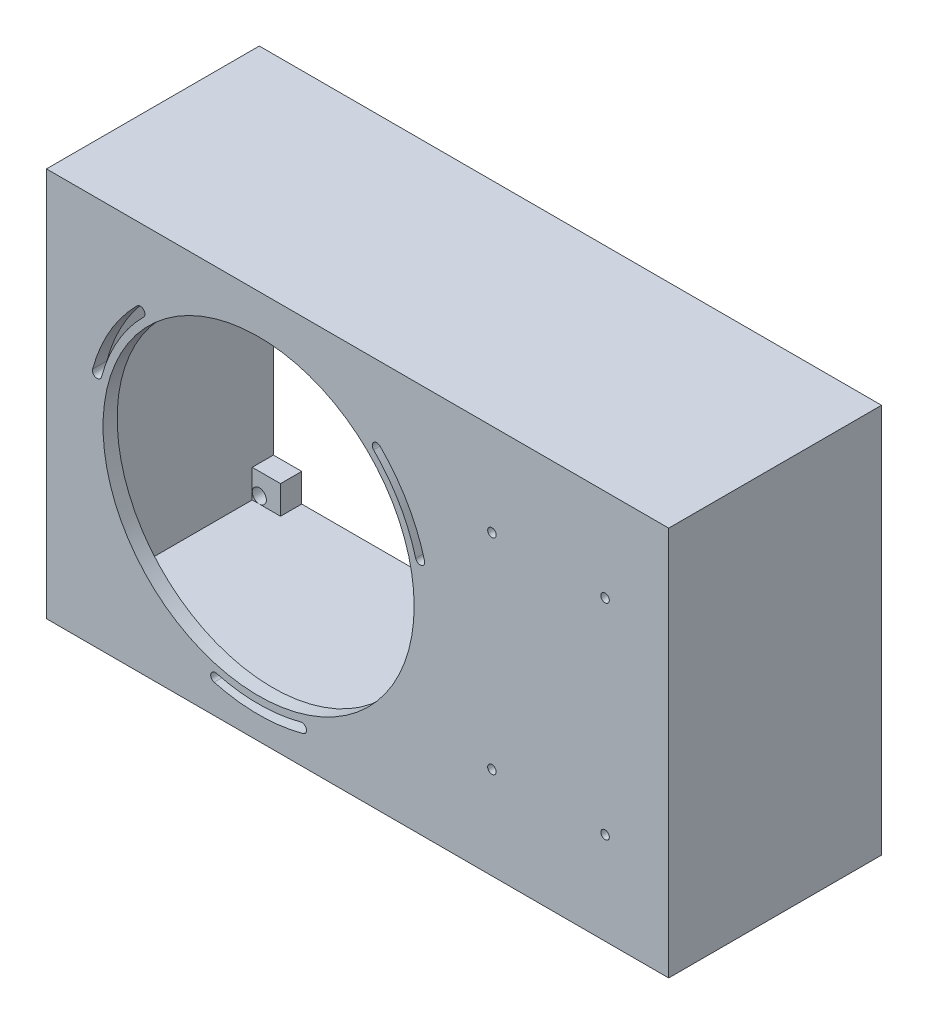
SolidWorks part; units mm, degrees
ref_plane "前视基准面" through (0, 0, 0) normal (0, 0, 1) x (1, 0, 0)
ref_plane "上视基准面" through (0, 0, 0) normal (0, 1, 0) x (1, 0, 0)
ref_plane "右视基准面" through (0, 0, 0) normal (1, 0, 0) x (0, 0, -1)
other "Configuration Table"
sketch "草图1" plane through (0, 0, 0) normal (0, 0, 1) x (1, 0, 0)
  line L1 (-44, -27.55) -> (44, -27.55)
  line L2 (-44, -27.55) -> (-44, 27.55)
  line L3 (-44, 27.55) -> (44, 27.55)
  line L4 (44, -27.55) -> (44, 27.55)
  line L5 (-44, -27.55) -> (44, 27.55) construction
  line L6 (-44, 27.55) -> (44, -27.55) construction
  line L7 (-42, -25.55) -> (42, -25.55)
  line L8 (-42, -25.55) -> (-42, 25.55)
  line L9 (-42, 25.55) -> (42, 25.55)
  line L10 (42, -25.55) -> (42, 25.55)
  line L11 (-42, -25.55) -> (42, 25.55) construction
  line L12 (-42, 25.55) -> (42, -25.55) construction
  point P0 (0, 0)
  point P6 (0, 0)
  dimension "D1" = 88
  dimension "D2" = 55.1
  dimension "D3" = 2
  dimension "D4" = 2
extrude "凸台-拉伸1" add sketch "草图1" along normal blind 30.1
sketch "草图2" plane through (0, 0, 30.1) normal (0, 0, 1) x (1, 0, 0)
  line L0 (-44, -27.55) -> (44, -27.55) construction
  line L1 (-44, 27.55) -> (16, 27.55)
  line L2 (-44, 27.55) -> (-44, -27.55)
  line L3 (-44, -27.55) -> (16, -27.55)
  line L4 (16, 27.55) -> (16, -27.55)
  line L5 (-14, 27.55) -> (-14, -27.55) construction
  line L6 (44, -27.55) -> (44, 27.55) construction
  line L7 (16, 27.55) -> (44, 27.55)
  line L8 (16, 27.55) -> (16, -27.55)
  line L9 (16, -27.55) -> (44, -27.55)
  line L10 (44, 27.55) -> (44, -27.55)
  line L11 (-30.7231, 16.7231) -> (-14, 0) construction
  line L12 (-14, 0) -> (-36.8441, 6.1211) construction
  line L13 (-20.1211, -22.8441) -> (-14, 0) construction
  line L14 (-14, 0) -> (-7.8789, -22.8441) construction
  line L15 (8.8441, 6.1211) -> (-14, 0) construction
  line L16 (2.7231, 16.7231) -> (-14, 0) construction
  line L17 (-34.4815, 11.825) -> (-14, 0) construction
  line L18 (-14, 0) -> (5.0526, 11) construction
  circle A0 centre (-14, 0) radius 22
  circle A1 centre (-14, 0) radius 24.3
  circle A2 centre (-30.7231, 16.7231) radius 0.65
  circle A3 centre (-36.8441, 6.1211) radius 0.65
  circle A4 centre (-14, 0) radius 23.65
  circle A5 centre (-20.1211, -22.8441) radius 0.65
  circle A6 centre (-7.8789, -22.8441) radius 0.65
  circle A7 centre (8.8441, 6.1211) radius 0.65
  circle A8 centre (2.7231, 16.7231) radius 0.65
  circle A11 centre (-14, 0) radius 23
  line M11 (42, 25.55) -> (42, -25.55)
  line M12 (42, -25.55) -> (-42, -25.55)
  line M14 (-42, 25.55) -> (42, 25.55)
  dimension "D2" = 44
  dimension "D3" = 2.3
  dimension "D4" = 30
  dimension "D12" = 1.3
  dimension "D1" = 60
  dimension "D5" = 120
  dimension "D6" = 30
  dimension "D7" = 30
  dimension "D8" = 120
  dimension "D9" = 15
  dimension "D10" = 15
  dimension "D11" = 15
extrude "凸台-拉伸2" add sketch "草图2" against normal blind 2 contours L4 M14 M12 M11 | L2 L3 L4 L1 | A0 region at (29, 0, 30.1)
extrude "切除-拉伸1" cut sketch "草图2<4>" against normal through all contours A2 A4 | A4 A2 | A2 A3 A4 | A11 A2 A4 A3 | A3 A4 | A4 A3 | A4 A5 | A4 A5 | A11 A5 A4 A6 | A5 A6 A4 | A4 A6 | A4 A6 | A4 A7 | A4 A7 | A7 A8 A4 | A11 A7 A4 A8 | A4 A8 | A4 A8 region at (6.5682, 11.875, 30.1) region at (9.1091, 6.1921, 30.1) region at (-14, -23.7501, 30.1) region at (-7.8079, -23.1091, 30.1) region at (2.917, 16.917, 30.1) region at (6.0039, 11.5492, 30.1) region at (8.5761, 6.0493, 30.1) region at (-20.1921, -23.1091, 30.1) region at (-7.9507, -22.5761, 30.1) region at (-14, -23.0985, 30.1) region at (-34.5682, 11.875, 30.1) region at (-30.917, 16.917, 30.1) region at (2.5269, 16.5269, 30.1) region at (-37.1091, 6.1921, 30.1) region at (-20.0493, -22.5761, 30.1) region at (-30.5269, 16.5269, 30.1) region at (-34.0039, 11.5492, 30.1) region at (-36.5761, 6.0493, 30.1)
sketch "草图2<4>" plane through (0, 0, 30.1) normal (0, 0, 1) x (1, 0, 0) same geometry as "草图2"
sketch "草图3" plane through (0, 0, 0) normal (0, 0, -1) x (-1, 0, 0)
  line L1 (-44, 27.55) -> (-38, 27.55)
  line L2 (-44, 27.55) -> (-44, 21.55)
  line L3 (-44, 21.55) -> (-38, 21.55)
  line L4 (-38, 27.55) -> (-38, 21.55)
  line L5 (44, 27.55) -> (38, 27.55)
  line L6 (44, 27.55) -> (44, 21.55)
  line L7 (44, 21.55) -> (38, 21.55)
  line L8 (38, 27.55) -> (38, 21.55)
  line L9 (-44, -27.55) -> (-38, -27.55)
  line L10 (-44, -27.55) -> (-44, -21.55)
  line L11 (-44, -21.55) -> (-38, -21.55)
  line L12 (-38, -27.55) -> (-38, -21.55)
  line L13 (44, -27.55) -> (38, -27.55)
  line L14 (44, -27.55) -> (44, -21.55)
  line L15 (44, -21.55) -> (38, -21.55)
  line L16 (38, -27.55) -> (38, -21.55)
  circle A0 centre (-41, 24.55) radius 1
  circle A1 centre (-41, -24.55) radius 1
  circle A2 centre (41, -24.55) radius 1
  circle A3 centre (41, 24.55) radius 1
  dimension "D4" = 2
  dimension "D1" = 6
  dimension "D2" = 3
  dimension "D3" = 3
  dimension "D5" = 3
  dimension "D6" = 3
extrude "凸台-拉伸3" add sketch "草图3" against normal blind 3 contours L12 L11 L10 L9 | L15 L16 L13 L14 | L3 L4 L1 L2 | L7 L8 L5 L6
extrude "切除-拉伸2" cut sketch "草图3<3>" against normal blind 3 contours A0 | A1 | A2 | A3
sketch "草图3<3>" plane through (0, 0, 0) normal (0, 0, -1) x (-1, 0, 0) same geometry as "草图3"
sketch "草图4" plane through (0, 0, 30.1) normal (0, 0, 1) x (1, 0, 0)
  line L8 (44, -27.55) -> (44, 27.55) construction
  line L9 (44, 27.55) -> (-44, 27.55) construction
  line L10 (-44, -27.55) -> (44, -27.55) construction
  circle A0 centre (19, 14.5) radius 0.6
  circle A1 centre (35, 14.5) radius 0.6
  circle A2 centre (19, -14.5) radius 0.6
  circle A3 centre (35, -14.5) radius 0.6
  point P8 (0, 0)
  point P9 (0, 0)
  point P10 (0, 0)
  point P11 (0, 0)
  dimension "D1" = 1.2
  dimension "D2" = 25
  dimension "D3" = 13.05
  dimension "D4" = 13.05
  dimension "D5" = 9
extrude "切除-拉伸3" cut sketch "草图4" against normal through all
